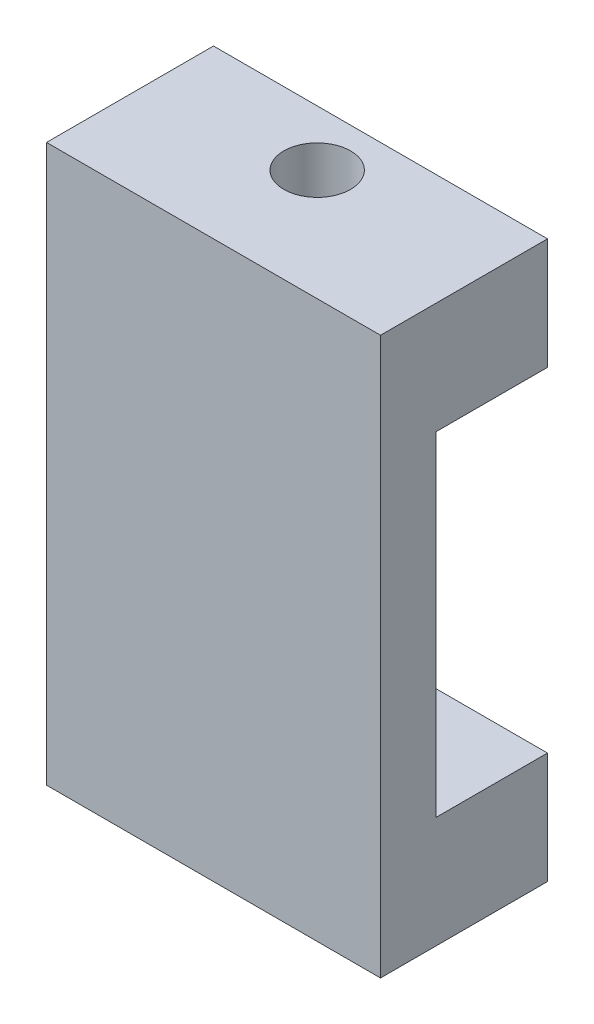
SolidWorks part; units mm, degrees
ref_plane "Front Plane" through (0, 0, 0) normal (0, 0, 1) x (1, 0, 0)
ref_plane "Top Plane" through (0, 0, 0) normal (0, 1, 0) x (1, 0, 0)
ref_plane "Right Plane" through (0, 0, 0) normal (1, 0, 0) x (0, 0, -1)
sketch "Sketch4" plane through (0, 0, 0) normal (0, 0, 1) x (1, 0, 0)
  line L1 (15, -15) -> (-15, -15)
  line L2 (15, -15) -> (15, 15)
  line L3 (15, 15) -> (-15, 15)
  line L4 (-15, -15) -> (-15, 15)
  line L5 (15, -15) -> (-15, 15) construction
  line L6 (15, 15) -> (-15, -15) construction
  circle A0 centre (0, 0) radius 15
  point P0 (0, 0)
  dimension "D1" = 30
extrude "Boss-Extrude2" add sketch "Sketch4" along normal blind 2.5 and the other way blind 2.5 contours A0 L3 L4 | A0 L4 L1 | A0 L1 L2 | A0 | A0 L2 L3 region at (11.6495, -11.6495, 0) region at (-11.6495, -11.6495, 0) region at (0, 0, 0) region at (11.6495, 11.6495, 0) region at (-11.6495, 11.6495, 0)
sketch "Sketch5" plane through (0, 15, 0) normal (0, 1, 0) x (1, 0, 0)
  line L0 (-15, 7.5) -> (15, 7.5) construction
  line L1 (-15, -2.5) -> (15, -2.5)
  line L2 (-15, -2.5) -> (-15, 12.5)
  line L3 (-15, 12.5) -> (15, 12.5)
  line L4 (15, -2.5) -> (15, 12.5)
  line L5 (15, 2.5) -> (-15, 2.5) construction
  circle A0 centre (-0.6856, 7.5) radius 3
  point P12 (-0.6856, 6.3905)
  dimension "D1" = 6
  dimension "D2" = 5
extrude "Boss-Extrude3" add sketch "Sketch5" along normal blind 10
mirror "Mirror1" about plane through (0, 0, 0) normal (0, 1, 0) of "Boss-Extrude3"
